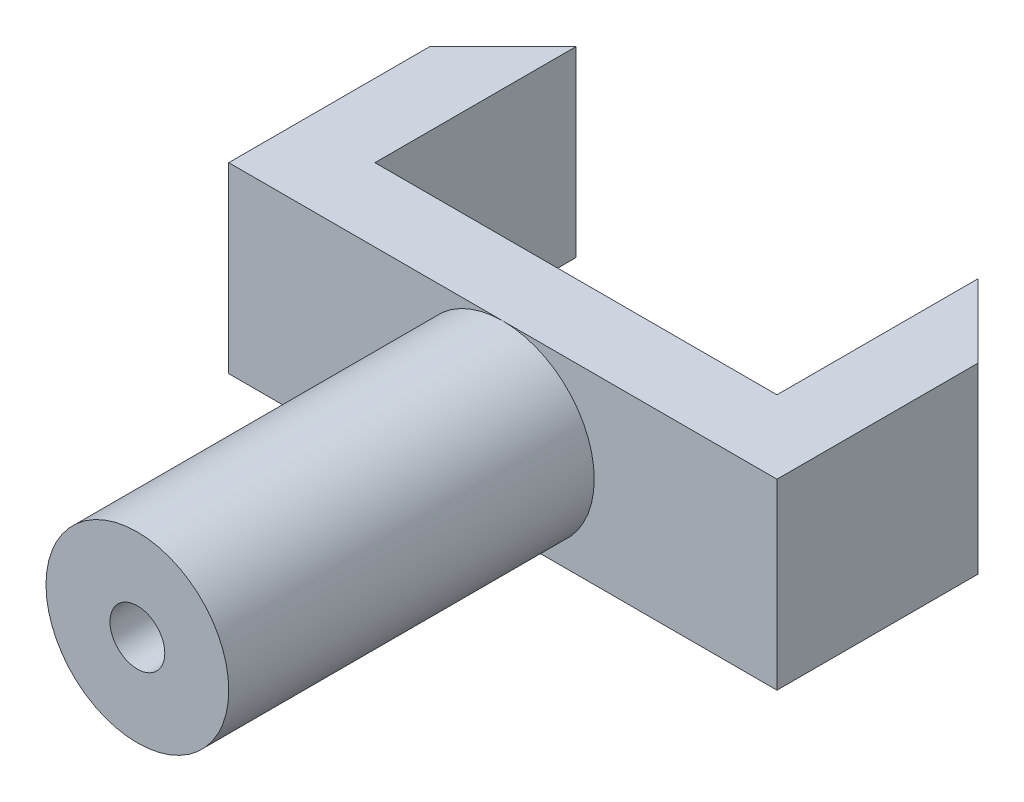
SolidWorks part; units mm, degrees
ref_plane "Front Plane" through (0, 0, 0) normal (0, 0, 1) x (1, 0, 0)
ref_plane "Top Plane" through (0, 0, 0) normal (0, 1, 0) x (1, 0, 0)
ref_plane "Right Plane" through (0, 0, 0) normal (1, 0, 0) x (0, 0, -1)
sketch "Sketch2" plane through (0, 0, 0) normal (0, 0, 1) x (1, 0, 0)
  circle A0 centre (0, 0) radius 15
  circle A1 centre (0, 0) radius 50
  dimension "D1" = 100
  dimension "D2" = 30
extrude "Boss-Extrude1" add sketch "Sketch2" along normal blind 200
sketch "Sketch3" plane through (0, 0, 0) normal (0, 0, -1) x (-1, 0, 0)
  line L0 (-150, 50) -> (-150, 33.4359)
  line L1 (-150, 33.4359) -> (-150, -50)
  line L2 (-150, 50) -> (150, 50)
  line L3 (150, 50) -> (150, -50)
  line L4 (-150, -50) -> (150, -50)
  dimension "D1" = 300
  dimension "D2" = 150
  dimension "D3" = 100
  dimension "D4" = 50
extrude "Boss-Extrude2" add sketch "Sketch3" along normal blind 40
sketch "Sketch4" plane through (0, 0, -40) normal (0, 0, -1) x (-1, 0, 0)
  line L0 (110, 50) -> (110, 33.8231)
  line L1 (150, 50) -> (-150, 50) construction
  line L2 (110, 33.8231) -> (110, -50)
  line L3 (-150, -50) -> (150, -50) construction
  line L4 (110, 50) -> (150, 50)
  line L5 (150, 50) -> (150, -50)
  line L6 (110, -50) -> (150, -50)
  line L7 (-110, 50) -> (-110, -50)
  line L8 (-150, -50) -> (-110, -50)
  line L9 (-110, 50) -> (-150, 50)
  line L10 (-150, 50) -> (-150, -50) construction
  line L11 (-150, 50) -> (-150, -50)
  dimension "D1" = 40
  dimension "D2" = 40
extrude "Boss-Extrude3" add sketch "Sketch4" along normal blind 120
chamfer "Chamfer1" distance 50 angle 45 1 edges at (-150, 0, -160)
chamfer "Chamfer2" distance 50 angle 45 1 edges at (150, 0, -160)
